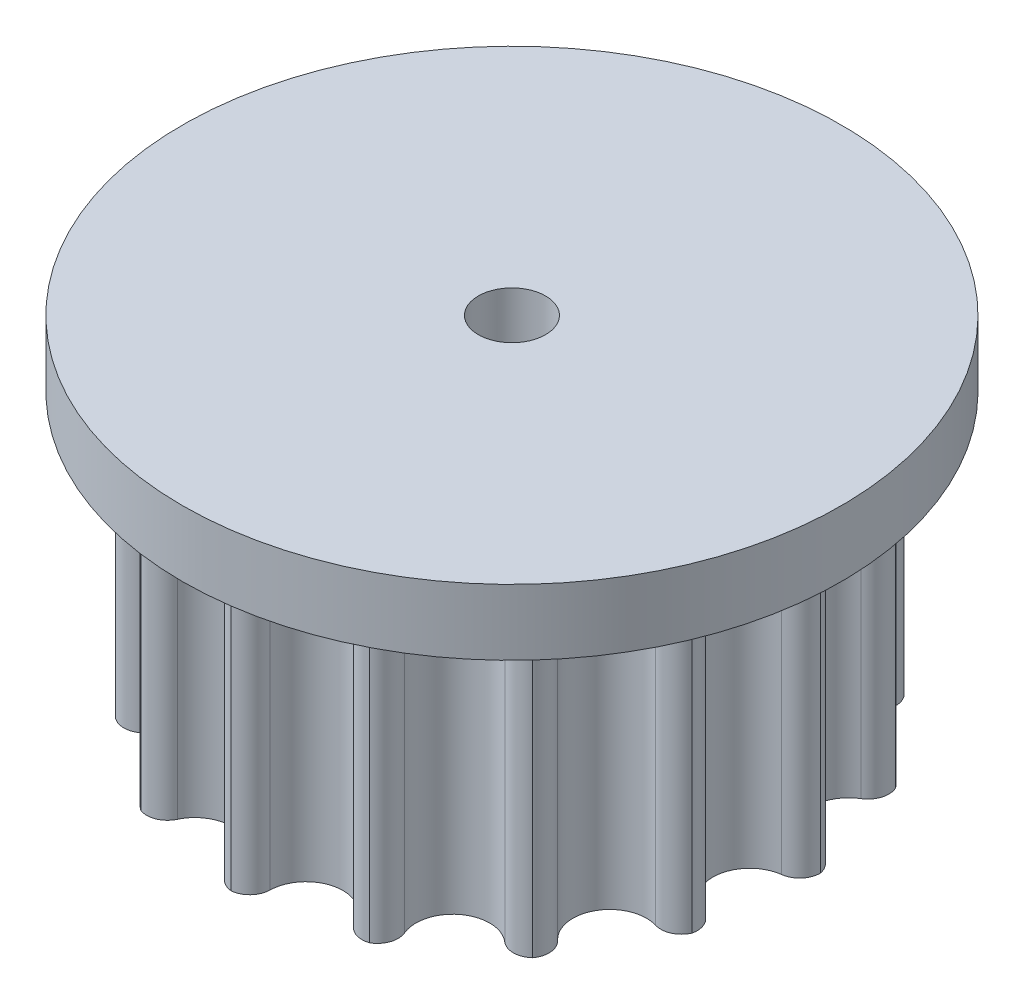
SolidWorks part; units mm, degrees
ref_plane "Front Plane" through (0, 0, 0) normal (0, 0, 1) x (1, 0, 0)
ref_plane "Top Plane" through (0, 0, 0) normal (0, 1, 0) x (1, 0, 0)
ref_plane "Right Plane" through (0, 0, 0) normal (1, 0, 0) x (0, 0, -1)
sketch "Sketch1" plane through (0, 0, 0) normal (0, 1, 0) x (1, 0, 0)
  line L0 (0, 0) -> (0, 6.7802) construction
  line L1 (0, 0) -> (2.6235, 5.8925) construction
  circle A0 centre (0, 0) radius 6.7802 construction
  circle A1 centre (0, 0) radius 5.5602 construction
  circle A2 centre (0, 6.4502) radius 0.89 construction
  circle A5 centre (2.6235, 5.8925) radius 0.89 construction
  arc A6 (0, 5.5602) -> (0.8665, 6.2469) centre (0, 6.4502) ccw
  arc A7 (0.8665, 6.2469) -> (1.461, 6.6209) centre (1.3532, 6.1327) cw
  arc A8 (1.3583, 6.6427) -> (1.7493, 6.0592) centre (1.2581, 6.1529) cw
  arc A9 (2.2615, 5.0795) -> (1.7493, 6.0592) centre (2.6235, 5.8925) cw
  arc A10 (1.461, 6.6209) -> (1.3583, 6.6427) centre (0, 0) cw
  arc A11 (0, 5.5602) -> (2.2615, 5.0795) centre (0, 0) ccw
  dimension "D1" = 13.5604
  dimension "D3" = 1.78
  dimension "D4" = 0.5
  dimension "D2" = 1.22
  dimension "D5" = 24
extrude "Boss-Extrude1" add sketch "Sketch1" along normal mid plane 7.112 contours A6 A11 A9 A8 A7 region at (0.0156, 0, -0.0736)
ref_axis "Axis1" through (0, 3.3, 0) along (0, -1, 0)
pattern_circular "CirPattern1" count 15 over 360 about axis through (0, 3.3, 0) along (0, -1, 0) of "Boss-Extrude1"
sketch "Sketch2" plane through (0, 0, 0) normal (1, 0, 0) x (0, 0, -1)
  line L10 (0, 3.5) -> (7.9549, 3.5) construction
  line L11 (0, 3.5) -> (0, 5.0875) construction
  line L12 (0, 5.0875) -> (7.9549, 5.0875) construction
  line L15 (7.9549, 3.5) -> (7.9549, 5.0875) construction
  line L20 (0, 3.3) -> (0, -3.3) construction
  line L22 (7.9549, 5.0875) -> (0, 5.0875)
  line L23 (7.9549, 5.0875) -> (7.9549, 3.5)
  line L24 (7.9549, 3.5) -> (0, 3.5)
  line L25 (0, 5.0875) -> (0, 3.5)
  dimension "D1" = 1.5875
  dimension "D2" = 7.9549
  dimension "D3" = 3.5
revolve "Revolve3" add sketch "Sketch2" angle 360 about axis through (0, 3.3, 0) along (0, -1, 0) region at (0, 4.2937, -3.9775)
mirror "Mirror1" [suppressed] about plane through (0, 0, 0) normal (0, 1, 0)
sketch "Sketch3" plane through (0, 0, 0) normal (0, -1, 0) x (-1, 0, 0)
  circle A0 centre (0, 0) radius 0.8112
  dimension "D1" = 1.6224
extrude "Cut-Extrude1" cut sketch "Sketch3" against normal through all both and the other way through all
equation "\"TEETH_NUM\"= 15"
equation "\"TOOTH_PITCH\"= 3mm"
equation "\"PITCH_LINE_OFFSET\"= .015in"
equation "\"DIAMETER_PER_GROOVE\"= \"OUTSIDE_DIAMETER\" / \"TEETH_NUM\" * 1in"
equation "\"PITCH_DIAMETER\"= ( ( \"TEETH_NUM\" * 3 - 1.31 ) / 3.1415 + .415 ) * 1mm"
equation "\"OUTSIDE_DIAMETER\"= \"PITCH_DIAMETER\" - \"PITCH_LINE_OFFSET\" * 2"
equation "\"D1@Sketch1\"=\"OUTSIDE_DIAMETER\""
equation "\"TOOTH_HEIGHT\"= 1.22mm"
equation "\"D2@Sketch1\"=\"TOOTH_HEIGHT\""
equation "\"TOOTH_DIAMETER\"= 1.78mm"
equation "\"INTERNAL_RADIUS\"= .5mm"
equation "\"D3@Sketch1\"=\"TOOTH_DIAMETER\""
equation "\"D5@Sketch1\"=360 / \"TEETH_NUM\""
equation "\"D4@Sketch1\"=\"INTERNAL_RADIUS\""
equation "\"D1@CirPattern1\"=\"TEETH_NUM\""
equation "\"BELT_GAP\"= 7mm"
equation "\"D2@Sketch2\"=\"PITCH_DIAMETER\"/2+1/32"
equation "\"D3@Sketch2\"=\"BELT_GAP\"/2"
equation "\"D1@Sketch3\"=\"PITCH_DIAMETER\"-.5"
